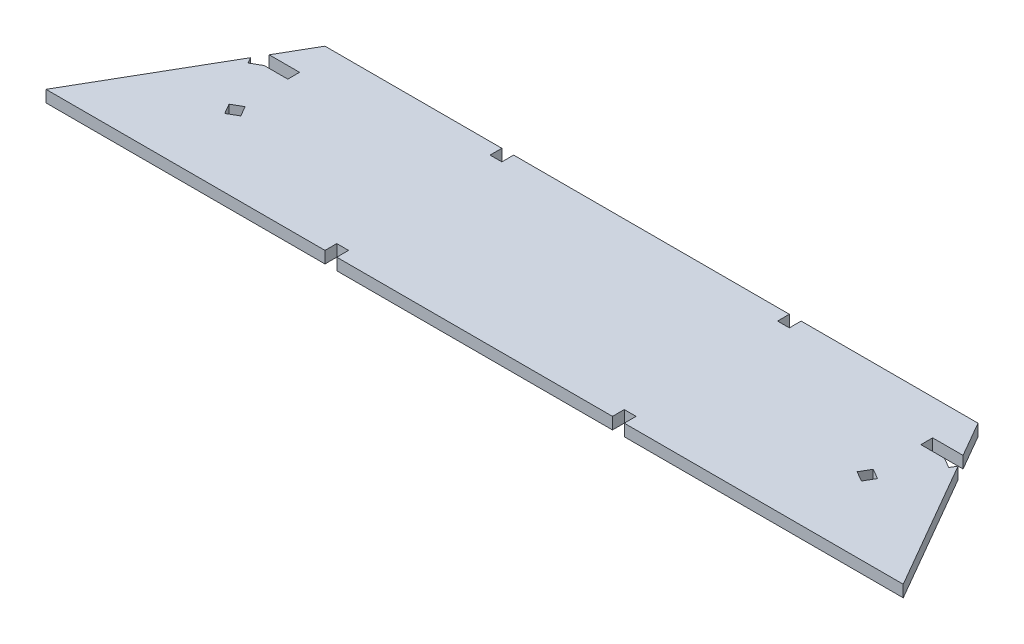
SolidWorks part; units mm, degrees
ref_plane "Front Plane" through (0, 0, 0) normal (0, 0, 1) x (1, 0, 0)
ref_plane "Top Plane" through (0, 0, 0) normal (0, 1, 0) x (1, 0, 0)
ref_plane "Right Plane" through (0, 0, 0) normal (1, 0, 0) x (0, 0, -1)
sketch "Sketch1" plane through (0, 609.6, 0) normal (0, 1, 0) x (1, 0, 0)
  line L12 (923.3117, 0) -> (461.6558, 799.6114)
  line L13 (461.6558, 799.6114) -> (-461.6558, 799.6114)
  line L14 (-461.6558, 799.6114) -> (-923.3117, 0)
  line L15 (-923.3117, 0) -> (-461.6558, -799.6114)
  line L16 (-461.6558, -799.6114) -> (461.6558, -799.6114)
  line L17 (461.6558, -799.6114) -> (923.3117, 0)
  line L18 (923.3117, 0) -> (461.6558, 799.6114)
  line L19 (461.6558, 799.6114) -> (-461.6558, 799.6114)
  line L20 (-461.6558, 799.6114) -> (-923.3117, 0)
  line L21 (-923.3117, 0) -> (-461.6558, -799.6114)
  line L22 (-461.6558, -799.6114) -> (461.6558, -799.6114)
  line L23 (461.6558, -799.6114) -> (923.3117, 0)
  line L24 (-351.6706, 609.1114) -> (-703.3412, 0)
  line L25 (-703.3412, 0) -> (-351.6706, -609.1114)
  line L26 (-351.6706, -609.1114) -> (351.6706, -609.1114)
  line L27 (351.6706, -609.1114) -> (703.3412, 0)
  line L28 (703.3412, 0) -> (351.6706, 609.1114)
  line L29 (351.6706, 609.1114) -> (-351.6706, 609.1114)
  line L30 (-351.6706, 609.1114) -> (-703.3412, 0)
  line L31 (-703.3412, 0) -> (-351.6706, -609.1114)
  line L32 (-351.6706, -609.1114) -> (351.6706, -609.1114)
  line L33 (351.6706, -609.1114) -> (703.3412, 0)
  line L34 (703.3412, 0) -> (351.6706, 609.1114)
  line L35 (351.6706, 609.1114) -> (-351.6706, 609.1114)
  dimension "D1" = 0
  dimension "D2" = 0
extrude "Boss-Extrude1" add sketch "Sketch1" against normal blind 12.7
sketch "Sketch2" plane through (0, 609.6, 0) normal (0, 1, 0) x (1, 0, 0)
  line L0 (-351.6706, -609.1114) -> (-461.6558, -799.6114)
  line L1 (-461.6558, -799.6114) -> (461.6558, -799.6114)
  line L2 (461.6558, -799.6114) -> (351.6706, -609.1114)
  line L3 (351.6706, -609.1114) -> (-351.6706, -609.1114)
extrude "Cut-Extrude1" cut sketch "Sketch2" against normal up to vertex (12.7 mm away) flip side to cut up to point (-461.6558, 596.9, 799.6114)
sketch "Sketch3" plane through (0, 609.6, 0) normal (0, 1, 0) x (1, 0, 0)
  line L4 (-148.4706, -609.1114) -> (-161.1706, -609.1114)
  line L5 (-148.4706, -621.8114) -> (-148.4706, -609.1114)
  line L6 (-161.1706, -621.8114) -> (-148.4706, -621.8114)
  line L7 (-161.1706, -609.1114) -> (-161.1706, -621.8114)
  line L8 (-148.4706, -609.1114) -> (-161.1706, -609.1114)
  line L9 (-148.4706, -621.8114) -> (-148.4706, -609.1114)
  line L10 (-161.1706, -621.8114) -> (-148.4706, -621.8114)
  line L11 (-161.1706, -609.1114) -> (-161.1706, -621.8114)
  line L12 (-342.9, -725.9025) -> (-331.9015, -719.5525)
  line L13 (-331.9015, -719.5525) -> (-338.2515, -708.554)
  line L14 (-338.2515, -708.554) -> (-349.25, -714.904)
  line L15 (-349.25, -714.904) -> (-342.9, -725.9025)
  line L16 (-342.9, -725.9025) -> (-331.9015, -719.5525)
  line L17 (-331.9015, -719.5525) -> (-338.2515, -708.554)
  line L18 (-338.2515, -708.554) -> (-349.25, -714.904)
  line L19 (-349.25, -714.904) -> (-342.9, -725.9025)
  line L20 (349.25, -714.904) -> (338.2515, -708.554)
  line L21 (338.2515, -708.554) -> (331.9015, -719.5525)
  line L22 (331.9015, -719.5525) -> (342.9, -725.9025)
  line L23 (342.9, -725.9025) -> (349.25, -714.904)
  line L24 (349.25, -714.904) -> (338.2515, -708.554)
  line L25 (338.2515, -708.554) -> (331.9015, -719.5525)
  line L26 (331.9015, -719.5525) -> (342.9, -725.9025)
  line L27 (342.9, -725.9025) -> (349.25, -714.904)
  line L28 (148.4706, -609.1114) -> (148.4706, -621.8114)
  line L29 (148.4706, -621.8114) -> (161.1706, -621.8114)
  line L30 (161.1706, -621.8114) -> (161.1706, -609.1114)
  line L31 (161.1706, -609.1114) -> (148.4706, -609.1114)
  line L32 (148.4706, -609.1114) -> (148.4706, -621.8114)
  line L33 (148.4706, -621.8114) -> (161.1706, -621.8114)
  line L34 (161.1706, -621.8114) -> (161.1706, -609.1114)
  line L35 (161.1706, -609.1114) -> (148.4706, -609.1114)
  line L36 (373.6677, -647.2114) -> (366.3353, -659.9114)
  line L37 (381, -659.9114) -> (373.6677, -647.2114)
  line L38 (377.3338, -666.2614) -> (381, -659.9114)
  line L39 (366.3353, -659.9114) -> (377.3338, -666.2614)
  line L40 (373.6677, -647.2114) -> (366.3353, -659.9114)
  line L41 (381, -659.9114) -> (373.6677, -647.2114)
  line L42 (377.3338, -666.2614) -> (381, -659.9114)
  line L43 (366.3353, -659.9114) -> (377.3338, -666.2614)
  line L44 (-373.6677, -647.2114) -> (-381, -659.9114)
  line L45 (-381, -659.9114) -> (-377.3338, -666.2614)
  line L46 (-377.3338, -666.2614) -> (-366.3353, -659.9114)
  line L47 (-366.3353, -659.9114) -> (-373.6677, -647.2114)
  line L48 (-373.6677, -647.2114) -> (-381, -659.9114)
  line L49 (-381, -659.9114) -> (-377.3338, -666.2614)
  line L50 (-377.3338, -666.2614) -> (-366.3353, -659.9114)
  line L51 (-366.3353, -659.9114) -> (-373.6677, -647.2114)
  dimension "D1" = 0
  dimension "D2" = 0
  dimension "D3" = 0
  dimension "D4" = 0
  dimension "D5" = 0
  dimension "D6" = 0
extrude "Cut-Extrude2" cut sketch "Sketch3" against normal up to vertex (12.7 mm away) up to point (-461.6558, 596.9, 799.6114)
sketch "Sketch4" plane through (0, 609.6, 0) normal (0, 1, 0) x (1, 0, 0)
  line L0 (-373.6677, -647.2114) -> (-340.9353, -647.2114)
  line L1 (-340.9353, -647.2114) -> (-340.9353, -659.9114)
  line L2 (-340.9353, -659.9114) -> (-366.3353, -659.9114)
  line L3 (-366.3353, -659.9114) -> (-373.6677, -647.2114)
  line L4 (0, -609.1114) -> (0, -799.6114)
  line L5 (-148.4706, -609.1114) -> (148.4706, -609.1114) construction
  line L6 (-461.6558, -799.6114) -> (461.6558, -799.6114) construction
  line L7 (340.9353, -659.9114) -> (366.3353, -659.9114)
  line L8 (340.9353, -647.2114) -> (340.9353, -659.9114)
  line L9 (373.6677, -647.2114) -> (340.9353, -647.2114)
  line L10 (366.3353, -659.9114) -> (373.6677, -647.2114)
  line M12 (366.3353, -659.9114) -> (373.6677, -647.2114)
extrude "Cut-Extrude3" cut sketch "Sketch4" against normal up to vertex (12.7 mm away) contours L9 L8 L7 M12 | L0 L1 L2 L3 region at (355.5455, 609.6, 653.2944) up to point (-461.6558, 596.9, 799.6114)
sketch "Sketch5" plane through (0, 609.6, 0) normal (0, 1, 0) x (1, 0, 0)
  line L0 (0, -609.1114) -> (0, -799.6114) construction
  line L1 (-148.4706, -609.1114) -> (148.4706, -609.1114) construction
  line L2 (-461.6558, -799.6114) -> (461.6558, -799.6114) construction
  line L3 (0, -704.3614) -> (250.1078, -704.3614) construction
  line L4 (-161.1706, -621.8114) -> (-148.4706, -621.8114) construction
  line L5 (148.4706, -609.1114) -> (148.4706, -621.8114) construction
  line L6 (148.4706, -621.8114) -> (161.1706, -621.8114) construction
  line L7 (161.1706, -621.8114) -> (161.1706, -609.1114) construction
  line L8 (-161.1706, -609.1114) -> (-161.1706, -621.8114) construction
  line L9 (-148.4706, -621.8114) -> (-148.4706, -609.1114) construction
  line L10 (-148.4706, -621.8114) -> (-148.4706, -609.1114) construction
  line L11 (-161.1706, -621.8114) -> (-148.4706, -621.8114) construction
  line L12 (-161.1706, -609.1114) -> (-161.1706, -621.8114) construction
  line L13 (161.1706, -621.8114) -> (161.1706, -609.1114) construction
  line L14 (148.4706, -621.8114) -> (161.1706, -621.8114) construction
  line L15 (148.4706, -609.1114) -> (148.4706, -621.8114) construction
  line L16 (148.4706, -799.6114) -> (148.4706, -786.9114)
  line L17 (148.4706, -786.9114) -> (161.1706, -786.9114)
  line L18 (161.1706, -786.9114) -> (161.1706, -799.6114)
  line L19 (-161.1706, -799.6114) -> (-161.1706, -786.9114)
  line L20 (-161.1706, -786.9114) -> (-148.4706, -786.9114)
  line L21 (-148.4706, -786.9114) -> (-148.4706, -799.6114)
  line L22 (-161.1706, -799.6114) -> (-148.4706, -799.6114)
  line L23 (148.4706, -799.6114) -> (161.1706, -799.6114)
  point P10 (-154.8206, -621.8114)
extrude "Cut-Extrude4" cut sketch "Sketch5" against normal up to vertex (12.7 mm away) up to point (-461.6558, 596.9, 799.6114)
